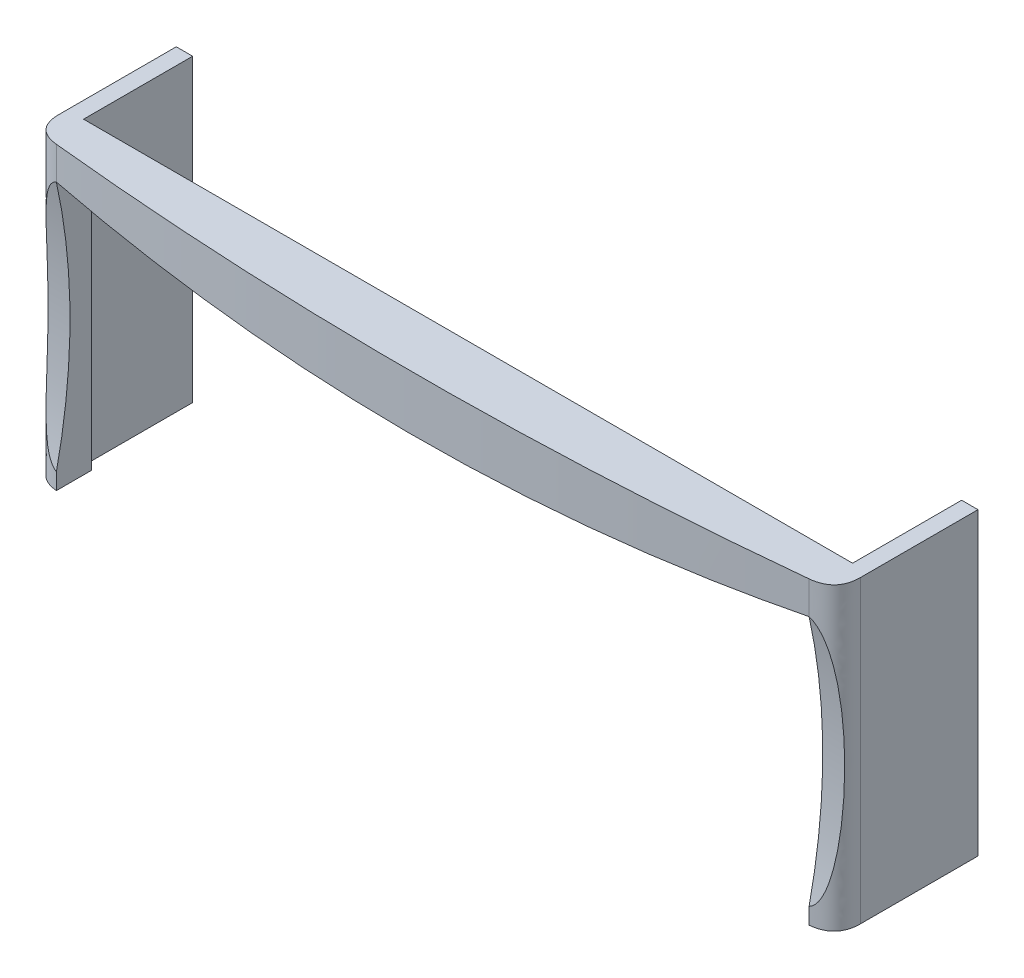
SolidWorks part; units mm, degrees
ref_plane "Front Plane" through (0, 0, 0) normal (0, 0, 1) x (1, 0, 0)
ref_plane "Top Plane" through (0, 0, 0) normal (0, 1, 0) x (1, 0, 0)
ref_plane "Right Plane" through (0, 0, 0) normal (1, 0, 0) x (0, 0, -1)
sketch "Sketch1" plane through (0, 0, 0) normal (0, 1, 0) x (1, 0, 0)
  line L0 (-73.5, 3) -> (-73.5, 13)
  line L1 (-70.5, 3) -> (70.5, 3)
  line L2 (-73.5, 3) -> (-73.5, -3)
  line L4 (73.5, 3) -> (73.5, -3)
  line L5 (-73.5, 3) -> (73.5, -3) construction
  line L6 (-73.5, -3) -> (73.5, 3) construction
  line L7 (-73.5, 13) -> (-70.5, 13)
  line L8 (-70.5, 13) -> (-70.5, 3)
  line L9 (73.5, 3) -> (73.5, 13)
  line L10 (73.5, 13) -> (70.5, 13)
  line L11 (70.5, 13) -> (70.5, 3)
  arc A0 (-73.5, -3) -> (73.5, -3) centre (0, 670.2812) ccw
  point P0 (0, 0)
  dimension "D1" = 6
  dimension "D2" = 147
  dimension "D3" = 10
  dimension "D4" = 10
  dimension "D5" = 3
  dimension "D6" = 3
extrude "Boss-Extrude1" add sketch "Sketch1" along normal blind 55
fillet "Fillet1" radius 5 2 edges at (73.5, 27.5, 3) (-73.5, 27.5, 3) conic rho 0.5
ref_plane "Plane2" through (0, 0, 10) normal (0, 0, 1) x (1, 0, 0)
sketch "Sketch2" plane through (0, 0, 10) normal (0, 0, 1) x (1, 0, 0)
  line L0 (-69.0095, 55) -> (-69.0095, 0) construction
  line L2 (-69.0095, 49) -> (-69.0095, 0)
  line L3 (-69.0095, 0) -> (69.0095, 0)
  line L4 (69.0095, 49) -> (69.0095, 0)
  line L5 (69.0095, 55) -> (-69.0095, 55) construction
  arc A0 (-69.0095, 49) -> (69.0095, 49) centre (0, 642.2882) ccw
  point P11 (0, 55)
  point P12 (0, 45)
  dimension "D1" = 6
  dimension "D2" = 10
  dimension "D3" = 49
extrude "Cut-Extrude1" cut sketch "Sketch2" against normal through all both and the other way through all
sketch "Sketch3" plane through (-73.5, 0, 0) normal (-1, 0, 0) x (0, 0, 1)
  line L0 (3.4751, 49) -> (3.4751, 3)
  line L1 (3.4751, 49) -> (3.4751, 0) construction
  arc A0 (3.4751, 49) -> (3.4751, 3) centre (108.0251, 26) ccw
  point P6 (0.9751, 26)
  point P8 (3.4751, 26)
  dimension "D1" = 3
  dimension "D2" = 2.5
extrude "Cut-Extrude2" cut sketch "Sketch3" against normal through all both
sketch "Sketch4" plane through (0, 0, -13) normal (0, 0, -1) x (-1, 0, 0)
  line L5 (70.5, 55) -> (70.5, 0)
  line L7 (70.5, 0) -> (73.5, 0)
  line L8 (73.5, 0) -> (73.5, 55)
  line L9 (73.5, 55) -> (70.5, 55)
  line L10 (70.5, 55) -> (70.5, 0)
  line L12 (70.5, 0) -> (73.5, 0)
  line L13 (73.5, 0) -> (73.5, 55)
  line L14 (73.5, 55) -> (70.5, 55)
  line L16 (-70.5, 0) -> (-70.5, 55)
  line L17 (-70.5, 55) -> (-73.5, 55)
  line L18 (-73.5, 55) -> (-73.5, 0)
  line L19 (-73.5, 0) -> (-70.5, 0)
  line L21 (-70.5, 0) -> (-70.5, 55)
  line L22 (-70.5, 55) -> (-73.5, 55)
  line L23 (-73.5, 55) -> (-73.5, 0)
  line L24 (-73.5, 0) -> (-70.5, 0)
  dimension "D1" = 0
  dimension "D2" = 0
extrude "Boss-Extrude2" add sketch "Sketch4" along normal blind 10
